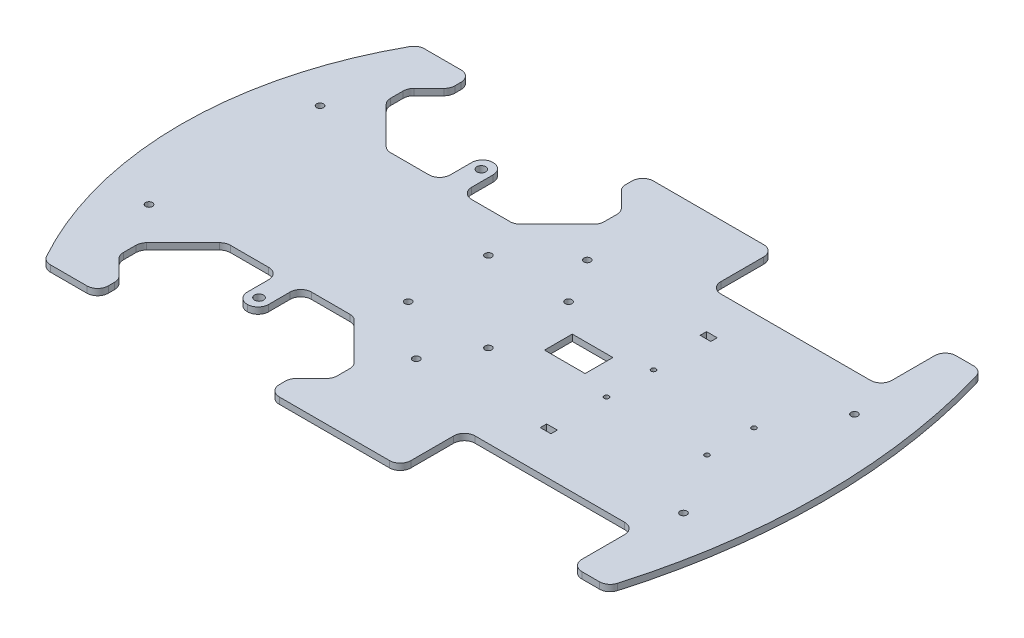
SolidWorks part; units mm, degrees
ref_plane "Front Plane" through (0, 0, 0) normal (0, 0, 1) x (1, 0, 0)
ref_plane "Top Plane" through (0, 0, 0) normal (0, 1, 0) x (1, 0, 0)
ref_plane "Right Plane" through (0, 0, 0) normal (1, 0, 0) x (0, 0, -1)
sketch "Sketch1" plane through (0, 0, 0) normal (0, 1, 0) x (1, 0, 0)
  line L1 (-150, -87.5) -> (150, -87.5) construction
  line L2 (-150, -87.5) -> (-150, 87.5) construction
  line L3 (-150, 87.5) -> (150, 87.5) construction
  line L4 (150, -87.5) -> (150, 87.5) construction
  line L5 (-150, -87.5) -> (150, 87.5) construction
  line L6 (-150, 87.5) -> (150, -87.5) construction
  line L7 (-91.537, 37.4826) -> (-31.537, 37.4826) construction
  line L9 (40, 87.5) -> (40, 57.5)
  line L10 (40, 57.5) -> (120, 57.5)
  line L11 (120, 57.5) -> (120, 87.5)
  line L12 (-150, 0) -> (150, 0) construction
  line L13 (-126.5544, 87.5) -> (-101.5544, 87.5)
  line L14 (120, -57.5) -> (120, -87.5)
  line L19 (56.9, -38.9) -> (61.9, -35.9) construction
  line L20 (56.9, 35.9) -> (61.9, 35.9)
  line L21 (40, -57.5) -> (120, -57.5)
  line L22 (40, -87.5) -> (40, -57.5)
  line L24 (-91.537, -37.4826) -> (-31.537, -37.4826) construction
  line L26 (-61.537, 37.4826) -> (-61.537, -37.4826) construction
  line L27 (56.9, 35.9) -> (56.9, 38.9)
  line L28 (-66.537, 37.4826) -> (-66.537, 57.4826)
  line L29 (-66.537, 57.4826) -> (-56.537, 57.4826)
  line L30 (-56.537, 57.4826) -> (-56.537, 37.4826)
  line L31 (-91.537, 37.4826) -> (-66.537, 37.4826)
  line L32 (-56.537, 37.4826) -> (-31.537, 37.4826)
  line L35 (-56.537, -57.4826) -> (-56.537, -37.4826)
  line L36 (-66.537, -57.4826) -> (-56.537, -57.4826)
  line L37 (-66.537, -37.4826) -> (-66.537, -57.4826)
  line L45 (80, 57.5) -> (80, -57.5) construction
  line L47 (40, 87.5) -> (-21.5544, 87.5)
  line L57 (-101.5544, 87.5) -> (-101.5544, 77.5)
  line L58 (-101.5544, 77.5) -> (-111.5544, 67.5)
  line L59 (-111.5544, 67.5) -> (-111.5544, 57.5)
  line L62 (-21.5544, 87.5) -> (-21.5544, 77.5)
  line L63 (-21.5544, 77.5) -> (-11.5544, 67.5)
  line L64 (-11.5544, 67.5) -> (-11.5544, 57.4651)
  line L65 (-11.5544, 57.4651) -> (-31.537, 37.4826)
  line L66 (-111.5544, 57.5) -> (-91.537, 37.4826)
  line L67 (-126.5544, -87.5) -> (-101.5544, -87.5)
  line L68 (-101.5544, -87.5) -> (-101.5544, -77.5)
  line L69 (-101.5544, -77.5) -> (-111.5544, -67.5)
  line L70 (-111.5544, -67.5) -> (-111.5544, -57.5)
  line L71 (-111.5544, -57.5) -> (-91.537, -37.4826)
  line L72 (-91.537, -37.4826) -> (-66.537, -37.4826)
  line L73 (-56.537, -37.4826) -> (-31.537, -37.4826)
  line L74 (-11.5544, -57.4651) -> (-31.537, -37.4826)
  line L75 (-11.5544, -67.5) -> (-11.5544, -57.4651)
  line L76 (-21.5544, -77.5) -> (-11.5544, -67.5)
  line L77 (-21.5544, -87.5) -> (-21.5544, -77.5)
  line L78 (40, -87.5) -> (-21.5544, -87.5)
  line L79 (120, -87.5) -> (136.956, -87.5)
  line L80 (120, 87.5) -> (136.956, 87.5)
  line L81 (56.9, 38.9) -> (61.9, 38.9)
  line L82 (61.9, 35.9) -> (61.9, 38.9)
  line L83 (56.9, 35.9) -> (61.9, 38.9) construction
  line L84 (56.9, 38.9) -> (61.9, 35.9) construction
  line L85 (56.9, -35.9) -> (61.9, -38.9) construction
  line L86 (61.9, -35.9) -> (61.9, -38.9)
  line L87 (56.9, -38.9) -> (61.9, -38.9)
  line L88 (56.9, -35.9) -> (56.9, -38.9)
  line L89 (56.9, -35.9) -> (61.9, -35.9)
  line L91 (26.5, -6.5) -> (45.5, -6.5)
  line L92 (26.5, -6.5) -> (26.5, 6.5)
  line L93 (26.5, 6.5) -> (45.5, 6.5)
  line L94 (45.5, -6.5) -> (45.5, 6.5)
  line L95 (26.5, -6.5) -> (45.5, 6.5) construction
  line L96 (26.5, 6.5) -> (45.5, -6.5) construction
  circle A3 centre (-61.537, 52) radius 2.1
  circle A4 centre (-61.537, -52) radius 2.1
  arc A7 (-126.5544, 87.5) -> (-126.5544, -87.5) centre (25, 0) ccw
  arc A10 (136.956, 87.5) -> (136.956, -87.5) centre (-150, 0) cw
  circle A11 centre (-125, -40) radius 1.6
  circle A12 centre (0, -40) radius 1.6
  circle A13 centre (125, -40) radius 1.6
  circle A14 centre (125, 40) radius 1.6
  circle A15 centre (0, 40) radius 1.6
  circle A16 centre (-125, 40) radius 1.6
  circle A17 centre (-25, 18.75) radius 1.6
  circle A18 centre (12.5, 18.75) radius 1.6
  circle A19 centre (12.5, -18.75) radius 1.6
  circle A20 centre (-25, -18.75) radius 1.6
  circle A21 centre (107, 11) radius 1.1
  circle A22 centre (60, 11) radius 1.1
  circle A23 centre (60, -11) radius 1.1
  circle A24 centre (107, -11) radius 1.1
  point P0 (0, 0)
  point P18 (59.4, 37.4)
  point P37 (59.4, -37.4)
  point P38 (0, 0)
  point P93 (36, 0)
  dimension "D15" = 20.1
  dimension "D19" = 4.2
  dimension "D21" = 3.2
  dimension "D23" = 125
  dimension "D24" = 175
  dimension "D26" = 3.2
  dimension "D28" = 80
  dimension "D34" = 300
  dimension "D22" = 3.2
  dimension "D16" = 3.2
  dimension "D38" = 3.2
  dimension "D40" = 2.2
  dimension "D1" = 175
  dimension "D2" = 300
  dimension "D3" = 25
  dimension "D4" = 10
  dimension "D5" = 135
  dimension "D6" = 135
  dimension "D7" = 80
  dimension "D8" = 30
  dimension "D9" = 25
  dimension "D10" = 30
  dimension "D11" = 10
  dimension "D12" = 5
  dimension "D13" = 3
  dimension "D14" = 20.6
  dimension "D17" = 20
  dimension "D18" = 10
  dimension "D20" = 52
  dimension "D25" = 10
  dimension "D27" = 125
  dimension "D29" = 10
  dimension "D30" = 135
  dimension "D31" = 10.0349
  dimension "D32" = 135
  dimension "D33" = 10
  dimension "D35" = 40
  dimension "D36" = 18.75
  dimension "D37" = 25
  dimension "D39" = 37.5
  dimension "D41" = 11
  dimension "D42" = 47
  dimension "D43" = 60
  dimension "D44" = 13
  dimension "D45" = 19
  dimension "D46" = 36
extrude "Boss-Extrude1" add sketch "Sketch1" along normal blind 3
fillet "Fillet1" radius 5 40 edges at (120, 1.5, 57.5) (120, 1.5, -57.5) (40, 1.5, -57.5) (40, 1.5, -87.5) (-21.5544, 1.5, -87.5) (40, 1.5, 57.5) (-56.537, 1.5, 37.4826) (-56.537, 1.5, 57.4826) (-66.537, 1.5, 57.4826) (-66.537, 1.5, 37.4826) (-56.537, 1.5, -37.4826) (-56.537, 1.5, -57.4826) (-66.537, 1.5, -57.4826) (-66.537, 1.5, -37.4826) (-91.537, 1.5, -37.4826) (-126.5544, 1.5, -87.5) (-126.5544, 1.5, 87.5) (40, 1.5, 87.5) (-21.5544, 1.5, 87.5) (-21.5544, 1.5, 77.5) (-11.5544, 1.5, 67.5) (-11.5544, 1.5, 57.4651) (-31.537, 1.5, 37.4826) (-91.537, 1.5, 37.4826) (-111.5544, 1.5, 67.5) (-111.5544, 1.5, 57.5) (-101.5544, 1.5, 77.5) (-101.5544, 1.5, 87.5) (-21.5544, 1.5, -77.5) (-11.5544, 1.5, -67.5) (-11.5544, 1.5, -57.4651) (-31.537, 1.5, -37.4826) (-111.5544, 1.5, -57.5) (-111.5544, 1.5, -67.5) (-101.5544, 1.5, -77.5) (-101.5544, 1.5, -87.5) (120, 1.5, -87.5) (136.956, 1.5, -87.5) (136.956, 1.5, 87.5) (120, 1.5, 87.5)
